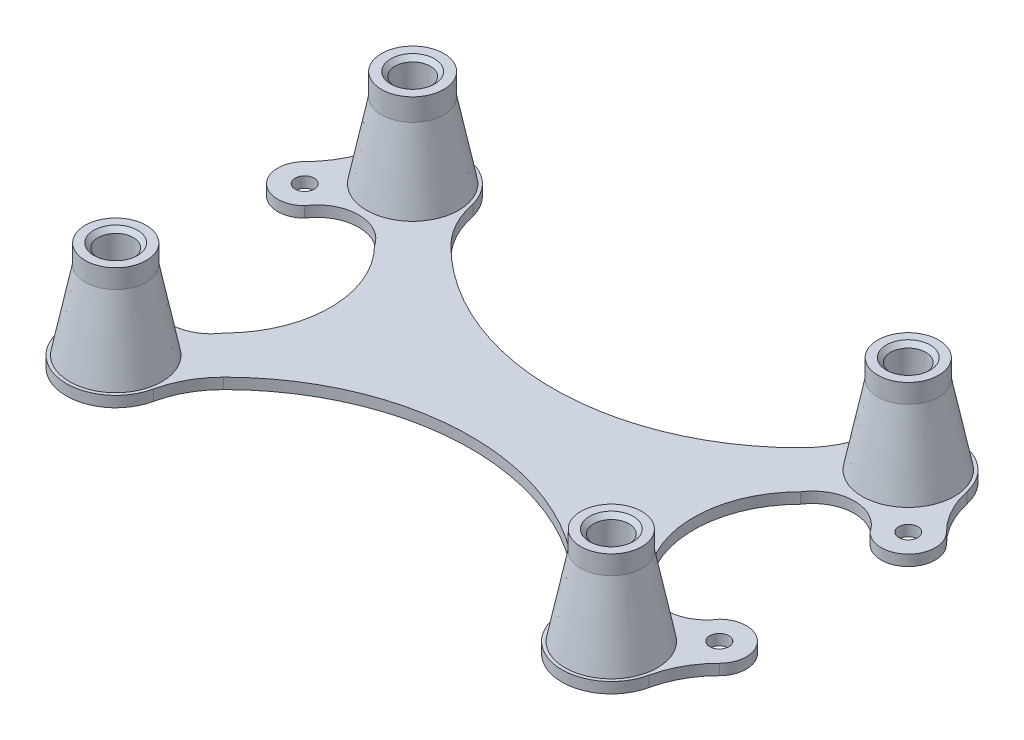
SolidWorks part; units mm, degrees
material "ABS"
ref_plane "Front Plane" through (0, 0, 0) normal (0, 0, 1) x (1, 0, 0)
ref_plane "Top Plane" through (0, 0, 0) normal (0, 1, 0) x (1, 0, 0)
ref_plane "Right Plane" through (0, 0, 0) normal (1, 0, 0) x (0, 0, -1)
sketch "Sketch1" plane through (0, 0, 0) normal (0, 1, 0) x (1, 0, 0)
  line L0 (-17.1901, 8.2099) -> (-8.2099, 17.1901) construction
  line L1 (-12.7, -12.7) -> (12.7, -12.7) construction
  line L2 (-12.7, -12.7) -> (-12.7, 12.7) construction
  line L3 (-12.7, 12.7) -> (12.7, 12.7) construction
  line L4 (12.7, -12.7) -> (12.7, 12.7) construction
  line L5 (-12.7, -12.7) -> (12.7, 12.7) construction
  line L6 (-12.7, 12.7) -> (12.7, -12.7) construction
  line L7 (8.2099, 17.1901) -> (17.1901, 8.2099) construction
  line L8 (-17.1901, -8.2099) -> (-8.2099, -17.1901) construction
  line L9 (8.2099, -17.1901) -> (17.1901, -8.2099) construction
  line L10 (99.3959, 8.2099) -> (108.3761, 17.1901) construction
  line L11 (103.886, -12.7) -> (129.286, -12.7) construction
  line L12 (103.886, -12.7) -> (103.886, 12.7) construction
  line L13 (103.886, 12.7) -> (129.286, 12.7) construction
  line L14 (129.286, -12.7) -> (129.286, 12.7) construction
  line L15 (103.886, -12.7) -> (129.286, 12.7) construction
  line L16 (103.886, 12.7) -> (129.286, -12.7) construction
  line L17 (124.7959, 17.1901) -> (133.7761, 8.2099) construction
  line L18 (99.3959, -8.2099) -> (108.3761, -17.1901) construction
  line L19 (124.7959, -17.1901) -> (133.7761, -8.2099) construction
  line L20 (-17.1901, -61.6401) -> (-8.2099, -52.6599) construction
  line L21 (-12.7, -82.55) -> (12.7, -82.55) construction
  line L22 (-12.7, -82.55) -> (-12.7, -57.15) construction
  line L23 (-12.7, -57.15) -> (12.7, -57.15) construction
  line L24 (12.7, -82.55) -> (12.7, -57.15) construction
  line L25 (-12.7, -82.55) -> (12.7, -57.15) construction
  line L26 (-12.7, -57.15) -> (12.7, -82.55) construction
  line L27 (8.2099, -52.6599) -> (17.1901, -61.6401) construction
  line L28 (-17.1901, -78.0599) -> (-8.2099, -87.0401) construction
  line L29 (8.2099, -87.0401) -> (17.1901, -78.0599) construction
  line L30 (99.3959, -61.6401) -> (108.3761, -52.6599) construction
  line L31 (103.886, -82.55) -> (129.286, -82.55) construction
  line L32 (103.886, -82.55) -> (103.886, -57.15) construction
  line L33 (103.886, -57.15) -> (129.286, -57.15) construction
  line L34 (129.286, -82.55) -> (129.286, -57.15) construction
  line L35 (103.886, -82.55) -> (129.286, -57.15) construction
  line L36 (103.886, -57.15) -> (129.286, -82.55) construction
  line L37 (124.7959, -52.6599) -> (133.7761, -61.6401) construction
  line L38 (99.3959, -78.0599) -> (108.3761, -87.0401) construction
  line L39 (124.7959, -87.0401) -> (133.7761, -78.0599) construction
  line L40 (12.7, -12.7) -> (103.886, -57.15) construction
  line L41 (12.7, -57.15) -> (103.886, -12.7) construction
  circle A2 centre (12.7, -12.7) radius 6.35
  circle A3 centre (-12.7, -12.7) radius 6.35
  circle A4 centre (0, 0) radius 7.325
  circle A5 centre (0, 0) radius 4.15
  circle A6 centre (0, -69.85) radius 11.6105
  circle A7 centre (116.586, -69.85) radius 11.6105
  arc A8 (-8.2099, -17.1901) -> (8.2099, -17.1901) centre (0, -22.4506) cw
  circle A9 centre (116.586, 0) radius 11.6105
  circle A12 centre (129.286, -12.7) radius 6.35
  circle A13 centre (103.886, -12.7) radius 6.35
  circle A14 centre (116.586, 0) radius 7.175
  circle A15 centre (116.586, 0) radius 4.15
  circle A16 centre (0, 0) radius 11.6105
  arc A17 (-17.1901, -8.2099) -> (-11.3418, 2.4833) centre (-32.5204, 7.1204) ccw
  arc A18 (108.3761, -17.1901) -> (124.7959, -17.1901) centre (116.586, -22.4506) cw
  arc A19 (17.1901, -8.2099) -> (11.2299, 2.9483) centre (32.5835, 7.1835) cw
  circle A20 centre (-12.7, -57.15) radius 6.35
  circle A21 centre (12.7, -57.15) radius 6.35
  circle A24 centre (0, -69.85) radius 7.175
  circle A25 centre (0, -69.85) radius 4.15
  arc A26 (-8.2099, -52.6599) -> (8.2099, -52.6599) centre (0, -47.3994) ccw
  arc A27 (99.3959, -8.2099) -> (105.3561, 2.9483) centre (84.0025, 7.1835) ccw
  arc A28 (133.7761, -8.2099) -> (127.9278, 2.4833) centre (149.1064, 7.1204) cw
  arc A29 (133.7761, -61.6401) -> (127.9278, -72.3333) centre (149.1064, -76.9704) ccw
  circle A30 centre (103.886, -57.15) radius 6.35
  circle A31 centre (129.286, -57.15) radius 6.35
  circle A34 centre (116.586, -69.85) radius 7.175
  circle A35 centre (116.586, -69.85) radius 4.15
  arc A36 (108.3761, -52.6599) -> (124.7959, -52.6599) centre (116.586, -47.3994) ccw
  arc A37 (99.3959, -61.6401) -> (105.2442, -72.3333) centre (84.0656, -76.9704) cw
  arc A38 (17.1901, -61.6401) -> (11.3418, -72.3333) centre (32.5204, -76.9704) ccw
  arc A39 (-17.1901, -61.6401) -> (-11.3418, -72.3333) centre (-32.5204, -76.9704) cw
  arc A40 (8.2099, -17.1901) -> (8.2099, -52.6599) centre (-9.525, -34.925) cw
  arc A41 (17.1901, -8.2099) -> (99.3959, -8.2099) centre (58.293, 32.893) ccw
  arc A42 (108.3761, -17.1901) -> (108.3761, -52.6599) centre (126.111, -34.925) ccw
  arc A43 (99.3959, -61.6401) -> (17.1901, -61.6401) centre (58.293, -102.743) ccw
  point P0 (0, 0)
  point P16 (-12.7, 12.7)
  point P19 (12.7, 12.7)
  point P22 (-12.7, -12.7)
  point P25 (12.7, -12.7)
  point P29 (116.586, 0)
  point P44 (103.886, 12.7)
  point P47 (129.286, 12.7)
  point P50 (103.886, -12.7)
  point P53 (129.286, -12.7)
  point P57 (0, -69.85)
  point P72 (-12.7, -57.15)
  point P75 (12.7, -57.15)
  point P78 (-12.7, -82.55)
  point P81 (12.7, -82.55)
  point P85 (116.586, -69.85)
  point P100 (103.886, -57.15)
  point P103 (129.286, -57.15)
  point P106 (103.886, -82.55)
  point P109 (129.286, -82.55)
  dimension "D1" = 8.3
  dimension "D3" = 3.175
  dimension "D5" = 8.3
  dimension "D6" = 12.7
  dimension "D9" = 8.3
  dimension "D10" = 12.7
  dimension "D13" = 8.3
  dimension "D14" = 12.7
  dimension "D15" = 14.35
  dimension "D17" = 14.35
  dimension "D18" = 14.35
  dimension "D19" = 25.0809
  dimension "D20" = 25.0809
  dimension "D21" = 58.1282
  dimension "D22" = 58.1282
  dimension "D23" = 12.7
  dimension "D4" = 25.4
  dimension "D7" = 69.85
  dimension "D8" = 25.4
  dimension "D11" = 116.586
  dimension "D12" = 25.4
  dimension "D16" = 25.4
extrude "Boss-Extrude1" add sketch "Sketch1" along normal blind 2.54 contours A3 A8 | A2 A6 A7 A3 A8 A4 | A2 A8 | A6 | A4 A5 | A5 | A7 | A43 A30 A42 A13 A41 A2 A40 A21 | A20 A26 | A21 A26 A20 A24 | A24 A25 | A21 A26 | A30 A36 | A31 A36 A30 A34 | A31 A36 | A13 A18 | A12 A13 A18 A14 | A34 A35 | A25 | A35 | A14 A15 | A15 | A12 A18 | A16 A19 A4 | A17 A3 A16 | A2 A19 A16 | A27 A9 A14 | A12 A28 A9 | A27 A13 A9 | A30 A37 A7 | A31 A7 A29 | A20 A39 A6 | A38 A21 A6 region at (12.7039, 0, 12.697) region at (58.293, 0, 34.925) region at (12.4175, 0, 4.4713) region at (0, 0, 12.1896) region at (0, 0, 11.2821) region at (103.8821, 0, 12.697) region at (104.1685, 0, 4.4713) region at (12.7039, 0, 57.153) region at (-12.7039, 0, 12.697) region at (-12.4175, 0, 4.4601) region at (105.8215, 0, 3.378) region at (116.586, 0, 12.1896) region at (0, 0, 57.6604) region at (103.8821, 0, 57.153) region at (129.0035, 0, 4.4601) region at (129.2899, 0, 12.697) region at (12.4175, 0, 65.3899) region at (10.4233, 0, 65.5325) region at (-12.7039, 0, 57.153) region at (104.1685, 0, 65.3899) region at (116.586, 0, 57.6604) region at (-12.4175, 0, 65.3899) region at (116.586, 0, 58.5679) region at (129.2899, 0, 57.153) region at (129.0035, 0, 65.3899) region at (-7.1178, 0, 0) region at (0, 0, 0) region at (109.6139, 0, 0) region at (116.586, 0, 0) region at (-6.9721, 0, 69.85) region at (0, 0, 69.85) region at (109.6139, 0, 69.85) region at (116.586, 0, 69.85)
extrude "Boss-Extrude2" add sketch "Sketch1<4>" along normal blind 25.4 contours A4 A5 | A14 A15 | A24 A25 | A34 A35 region at (-7.1178, 0, 0) region at (109.6139, 0, 0) region at (-6.9721, 0, 69.85) region at (109.6139, 0, 69.85)
sketch "Sketch1<4>" plane through (0, 0, 0) normal (0, 1, 0) x (1, 0, 0) same geometry as "Sketch1"
hole_wizard "#8 Clearance Hole2" positions "Sketch6" profile "Sketch7" hole size "#8" standard "ANSI Inch" end condition through all
sketch "Sketch6" plane through (0, 2.54, 0) normal (0, 1, 0) x (1, 0, 0)
  point P6 (129.286, -12.7)
  point P9 (129.286, -57.15)
  point P24 (-12.7, -57.15)
  point P28 (-12.7, -12.7)
sketch "Sketch7" plane through (129.286, 2.54, 12.7) normal (1, 0, 0) x (0, 0, 1)
  line L0 (0, 0) -> (0, 2.54)
  line L1 (0, 2.54) -> (2.2479, 2.54)
  line L2 (2.2479, 2.54) -> (2.2479, 0)
  line L5 (2.2479, 0) -> (0, 0)
  line L11 (0, -6.35) -> (0, 107.95) construction
  dimension "Thru Hole Dia." = 4.4958
  dimension "Thru Hole Depth" = 2.54
sketch "Sketch8" plane through (0, 0, 0) normal (1, 0, 0) x (0, 0, -1)
  line L0 (10.8569, 2.54) -> (7.0469, 21.59)
  line L1 (11.6105, 2.54) -> (2.4833, 2.54) construction
  line L2 (7.0469, 21.59) -> (7.0469, 2.54)
  line L3 (7.0469, 2.54) -> (10.8569, 2.54)
  line L4 (0, 0) -> (0, 30.7064) construction
  dimension "D1" = 19.05
  dimension "D2" = 3.81
revolve "Revolve1" add sketch "Sketch8" angle 360 about L4
sketch "Sketch9" plane through (0, 0, 0) normal (0, 1, 0) x (1, 0, 0)
  line L0 (-8.2742, -34.6778) -> (140.5133, -34.6778) construction
  line L1 (66.1196, -79.6601) -> (66.1196, 9.6453) construction
pattern_linear "LPattern1" count 2 spacing 116.586 along (1, 0, 0) count 2 spacing 69.85 along (0, 0, 1) of "Revolve1"
chamfer "Chamfer1" distance 1 angle 45 4 edges at (116.586, 25.4, 74) (116.586, 25.4, 4.15) (0, 25.4, 74) (0, 25.4, 4.15)
